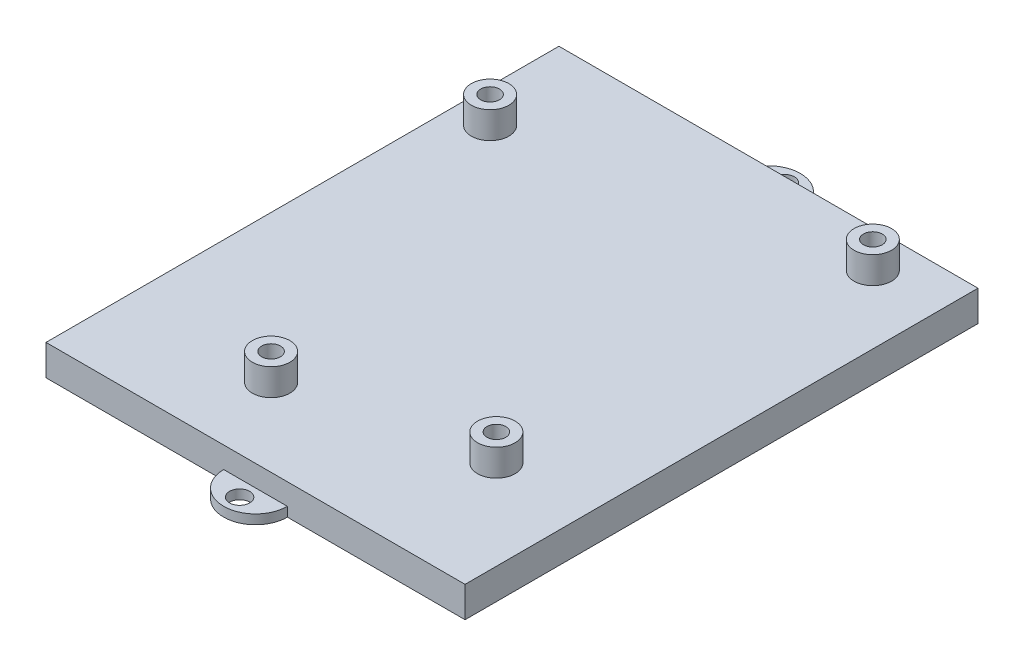
SolidWorks part; units mm, degrees
ref_plane "Front Plane" through (0, 0, 0) normal (0, 0, 1) x (1, 0, 0)
ref_plane "Top Plane" through (0, 0, 0) normal (0, 1, 0) x (1, 0, 0)
ref_plane "Right Plane" through (0, 0, 0) normal (1, 0, 0) x (0, 0, -1)
sketch "Sketch1" plane through (0, 0, 0) normal (0, 1, 0) x (1, 0, 0)
  line L0 (-31.25, 38.25) -> (31.25, 38.25)
  line L5 (-31.25, 38.25) -> (-31.25, -38.25)
  line L6 (-31.25, -38.25) -> (31.25, -38.25)
  line L7 (31.25, 38.25) -> (31.25, -38.25)
  point P11 (-31.25, 0)
  point P12 (0, -38.25)
  dimension "D3" = 76.5
  dimension "D4" = 62.5
extrude "Boss-Extrude1" add sketch "Sketch1" along normal blind 4.575
sketch "Sketch2" plane through (0, 4.575, 0) normal (0, 1, 0) x (1, 0, 0)
  line L0 (17.8977, -20.2309) -> (6.2677, 29.2199) construction
  line L1 (21.1029, 32.709) -> (6.2677, 29.2199) construction
  line L2 (17.8977, -20.2309) -> (-9.3002, -26.6274) construction
  line L3 (-9.3002, -26.6274) -> (-21.221, 24.0597) construction
  line L4 (0, -38.25) -> (0, 38.25) construction
  line L5 (-31.25, 0) -> (31.25, 0) construction
  line L6 (-21.221, 24.0597) -> (-26.1661, 22.8967) construction
  line L11 (-31.25, 38.25) -> (-31.25, -38.25) construction
  line L12 (-31.25, -38.25) -> (31.25, -38.25) construction
  line L13 (31.25, 38.25) -> (-31.25, 38.25) construction
  line L14 (31.25, -38.25) -> (31.25, 38.25) construction
  circle A0 centre (17.8977, -20.2309) radius 2.8
  circle A1 centre (21.1029, 32.709) radius 2.8
  circle A2 centre (-26.1661, 22.8967) radius 2.8
  circle A3 centre (-9.3002, -26.6274) radius 2.8
  circle A4 centre (21.1029, 32.709) radius 1.4
  circle A5 centre (17.8977, -20.2309) radius 1.4
  circle A6 centre (-9.3002, -26.6274) radius 1.4
  circle A7 centre (-26.1661, 22.8967) radius 1.4
  point P20 (0, 0)
  point P28 (0, -45)
  point P29 (0, -38.25)
  point P31 (0, 0)
  point P32 (-9.3002, -26.6274)
  point P33 (0, 0)
  point P34 (-31.25, 0)
  point P37 (45, 0)
  point P38 (0, 0)
  point P39 (0, 0)
  point P41 (0, 38.25)
  point P44 (31.25, 0)
  dimension "D7" = 2.8
  dimension "D10" = 1.4
  dimension "D1" = 27.94
  dimension "D2" = 15.24
  dimension "D3" = 5.08
  dimension "D4" = 1.27
  dimension "D5" = 50.8
  dimension "D6" = 13.235
  dimension "D8" = 9.3002
  dimension "D9" = 26.6274
extrude "Boss-Extrude2" add sketch "Sketch2" along normal blind 4
sketch "Sketch3" plane through (0, 4.575, 0) normal (0, 1, 0) x (1, 0, 0)
  circle A0 centre (17.8977, -20.2309) radius 1.4
  circle A1 centre (-9.3002, -26.6274) radius 1.4
  circle A2 centre (-26.1661, 22.8967) radius 1.4
  circle A3 centre (21.1029, 32.709) radius 1.4
  circle A4 centre (21.1029, 32.709) radius 1.4 construction
  circle A5 centre (-26.1661, 22.8967) radius 1.4 construction
extrude "Cut-Extrude1" cut sketch "Sketch3" against normal offset from surface (3.575 mm away) 1 up to face at (0, 0, 0)
sketch "Sketch4" plane through (0, 0, 0) normal (0, 1, 0) x (1, 0, 0)
  line L0 (-4.75, -38.25) -> (4.75, -38.25)
  line L2 (-31.25, -38.25) -> (31.25, -38.25) construction
  line L4 (0, -38.25) -> (0, -43) construction
  arc A0 (-4.75, -38.25) -> (4.75, -38.25) centre (0, -38.25) ccw
  circle A2 centre (0, -40.625) radius 1.5
  point P6 (0, -40.625)
  dimension "D2" = 3
  dimension "D3" = 4.75
extrude "Boss-Extrude3" add sketch "Sketch4" along normal blind 1.4
mirror "Mirror1" about plane through (0, 0, 0) normal (0, 0, 1) of "Boss-Extrude3"
